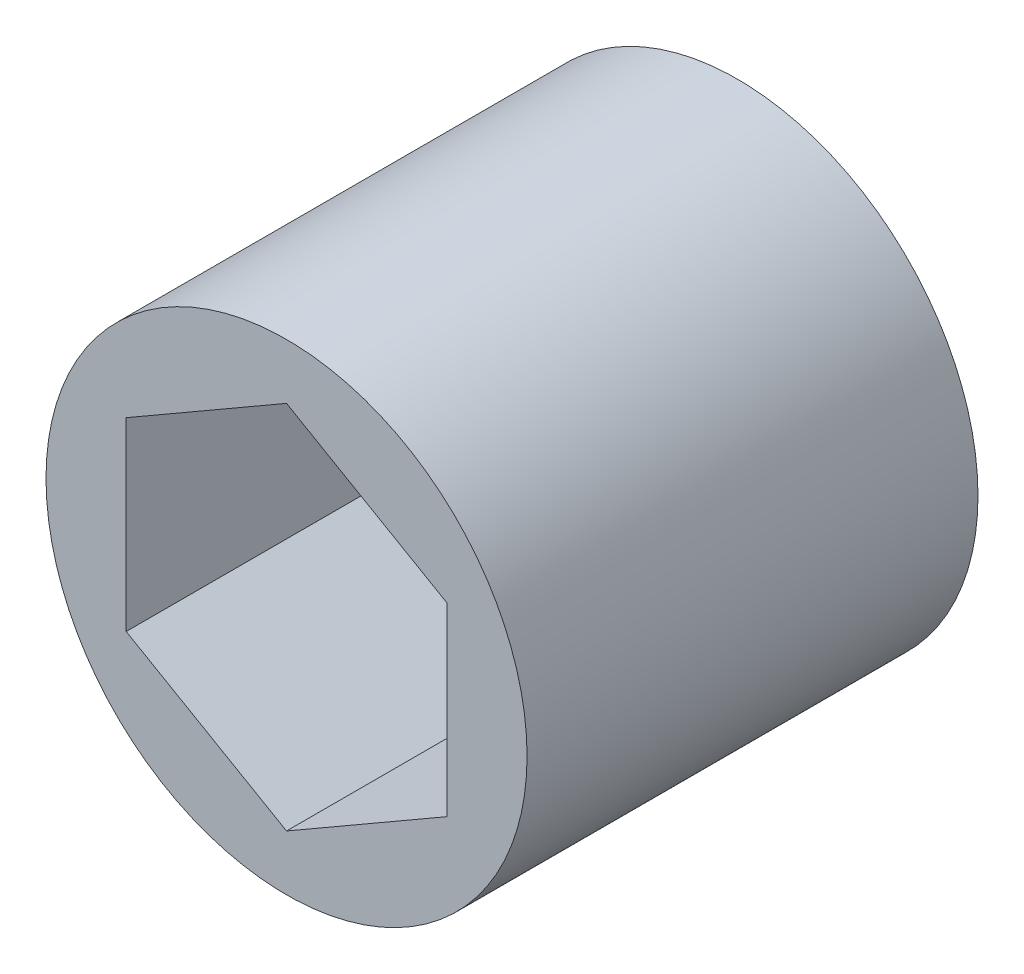
SolidWorks part; units mm, degrees
material "Nylon 101"
ref_plane "Front Plane" through (0, 0, 0) normal (0, 0, 1) x (1, 0, 0)
ref_plane "Top Plane" through (0, 0, 0) normal (0, 1, 0) x (1, 0, 0)
ref_plane "Right Plane" through (0, 0, 0) normal (1, 0, 0) x (0, 0, -1)
sketch "Sketch1" plane through (0, 0, 0) normal (0, 0, 1) x (1, 0, 0)
  line L1 (0, 7.3323) -> (-6.35, 3.6662)
  line L2 (-6.35, 3.6662) -> (-6.35, -3.6662)
  line L3 (-6.35, -3.6662) -> (0, -7.3323)
  line L4 (0, -7.3323) -> (6.35, -3.6662)
  line L5 (6.35, -3.6662) -> (6.35, 3.6662)
  line L6 (6.35, 3.6662) -> (0, 7.3323)
  circle A0 centre (0, 0) radius 6.35 construction
  circle A1 centre (0, 0) radius 9.525
  dimension "D1" = 19.05
  dimension "D2" = 12.7
extrude "Boss-Extrude1" add sketch "Sketch1" along normal mid plane 17.8562
